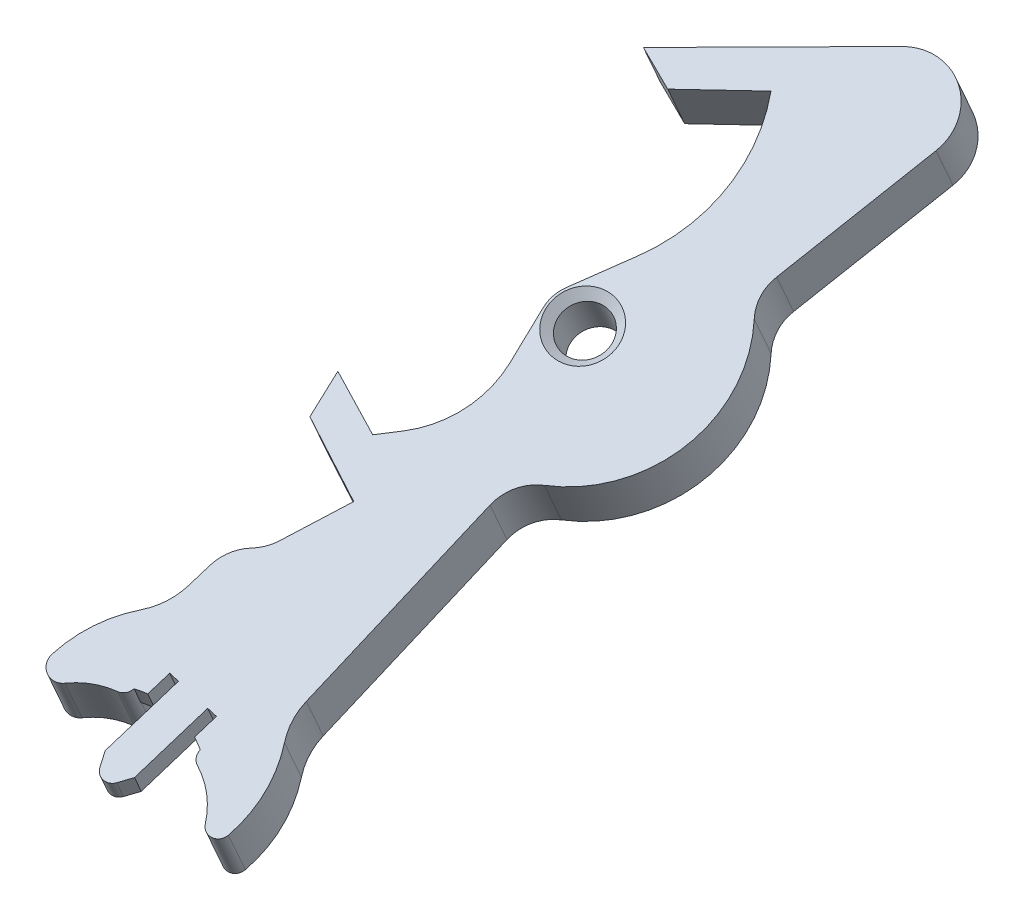
SolidWorks part; units mm, degrees
ref_plane "Plan de face" through (0, 0, 0) normal (0, 0, 1) x (1, 0, 0)
ref_plane "Plan de dessus" through (0, 0, 0) normal (0, 1, 0) x (1, 0, 0)
ref_plane "Plan de droite" through (0, 0, 0) normal (1, 0, 0) x (0, 0, -1)
ref_plane "Plan1" through (6.4076, 24.4468, 14.3554) normal (0.2205, 0.8411, 0.4939) x (-0.9673, 0.2535, 0)
sketch "Esquisse1" plane through (6.4076, 24.4468, 14.3554) normal (0.2205, 0.8411, 0.4939) x (-0.9673, 0.2535, 0)
  line L0 (8.3108, -19.2013) -> (8.287, -20.2463)
  line L1 (8.287, -20.2463) -> (5.8877, -20.1917)
  line L2 (5.8877, -20.1917) -> (5.9114, -19.1468)
  line L3 (5.4159, -18.9439) -> (5.4244, -18.5688)
  line L4 (3.8694, -21.6822) -> (4.3684, -33.2537)
  line L5 (2.9658, -43.5208) -> (2.0143, -51.4977)
  line L6 (5.7057, -53.4454) -> (12.5394, -47.4699)
  line L7 (12.5394, -47.4699) -> (10.7754, -46.9416)
  line L8 (10.7754, -46.9416) -> (7.9879, -49.2605)
  line L9 (7.0808, -41.9184) -> (8.3544, -38.9103)
  line L10 (8.3544, -38.9103) -> (6.9616, -33.8048)
  line L11 (6.9616, -33.8048) -> (9.3087, -31.1351)
  line L12 (9.3087, -31.1351) -> (11.9385, -31.9936)
  line L13 (11.9385, -31.9936) -> (11.4603, -30.1656)
  line L14 (11.4603, -30.1656) -> (8.02, -28.9566)
  line L15 (8.02, -28.9566) -> (8.9263, -26.2414)
  line L16 (10.1164, -23.9748) -> (10.1637, -21.8969)
  line L17 (8.8235, -18.6461) -> (8.815, -19.0212)
  arc A0 (5.9114, -19.1468) -> (5.4159, -18.9439) centre (7.6542, -14.1836) cw
  arc A1 (5.4244, -18.5688) -> (3.2945, -17.127) centre (6.1546, -15.196) cw
  arc A2 (3.2945, -17.127) -> (2.3817, -17.3668) centre (2.8801, -17.4067) ccw
  arc A3 (2.3817, -17.3668) -> (3.8694, -21.6822) centre (8.0635, -17.8222) ccw
  arc A4 (4.3684, -33.2537) -> (2.9658, -43.5208) centre (6.665, -38.7968) ccw
  arc A5 (2.0143, -51.4977) -> (5.7057, -53.4454) centre (4.2341, -51.7625) ccw
  arc A6 (7.9879, -49.2605) -> (7.0808, -41.9184) centre (13.8952, -44.8036) cw
  arc A7 (8.9263, -26.2414) -> (9.4702, -25.402) centre (10.8234, -26.8746) cw
  arc A8 (9.4702, -25.402) -> (10.1164, -23.9748) centre (8.1169, -23.9293) ccw
  arc A9 (10.1637, -21.8969) -> (11.9147, -18.0509) centre (6.2212, -17.7803) ccw
  arc A10 (11.9147, -18.0509) -> (10.7871, -17.58) centre (11.2655, -18.0201) ccw
  arc A11 (10.7871, -17.58) -> (8.8235, -18.6461) centre (8.2474, -15.2436) cw
  arc A12 (8.815, -19.0212) -> (8.3108, -19.2013) centre (6.7954, -14.1641) cw
extrude "Boss.-Extru.1" add sketch "Esquisse1" against normal blind 1.2
sketch "Esquisse2" plane through (6.143, 23.4375, 13.7628) normal (-0.2205, -0.8411, -0.4939) x (0.9754, -0.1901, -0.1116)
  line L0 (-7.7323, -33.2616) -> (-7.4927, -31.3873)
  line L1 (-7.4927, -31.3873) -> (-4.2361, -29.7466)
  line L2 (-4.2361, -29.7466) -> (-5.4835, -27.1702)
  line L3 (-6.9548, -25.0751) -> (-7.2684, -23.0206)
  line L4 (-6.3567, -19.6246) -> (-6.1135, -21.2181)
  line L5 (-6.1135, -21.2181) -> (-2.7524, -20.7051)
  line L6 (-2.7524, -20.7051) -> (-2.9956, -19.1115)
  line L7 (-1.0537, -21.9995) -> (-0.0631, -33.5394)
  line L8 (2.6461, -43.5414) -> (4.6138, -51.3301)
  line L9 (1.203, -53.7356) -> (-6.3413, -48.6869)
  line L10 (-6.3413, -48.6869) -> (-4.6597, -47.9365)
  line L11 (-4.6597, -47.9365) -> (-1.5976, -49.8784)
  line L12 (-1.6406, -42.4806) -> (-3.2899, -39.6609)
  line L13 (-3.2899, -39.6609) -> (-2.564, -34.4188)
  line L14 (-2.564, -34.4188) -> (-5.2344, -32.0726)
  line L15 (-5.2344, -32.0726) -> (-7.7323, -33.2616)
  arc A0 (-5.4835, -27.1702) -> (-6.1306, -26.4076) centre (-7.2836, -28.0418) ccw
  arc A1 (-6.1306, -26.4076) -> (-6.9548, -25.0751) centre (-4.9776, -24.7734) cw
  arc A2 (-7.2684, -23.0206) -> (-9.4987, -19.4312) centre (-3.887, -18.4318) cw
  arc A3 (-9.4987, -19.4312) -> (-8.4409, -18.8194) centre (-8.8588, -19.3172) cw
  arc A4 (-8.4409, -18.8194) -> (-6.3567, -19.6246) centre (-6.2221, -16.1763) ccw
  arc A5 (-2.9956, -19.1115) -> (-1.0684, -17.4082) centre (-4.1528, -15.8604) ccw
  arc A6 (-1.0684, -17.4082) -> (-0.1324, -17.5288) centre (-0.6215, -17.6324) cw
  arc A7 (-0.1324, -17.5288) -> (-1.0537, -21.9995) centre (-5.7087, -18.7099) cw
  arc A8 (-0.0631, -33.5394) -> (2.6461, -43.5414) centre (-1.629, -39.3314) cw
  arc A9 (4.6138, -51.3301) -> (1.203, -53.7356) centre (2.4464, -51.8777) cw
  arc A10 (-1.5976, -49.8784) -> (-1.6406, -42.4806) centre (-8.0282, -46.2167) ccw
extrude "Boss.-Extru.2" add sketch "Esquisse2" along normal blind 1.8
sketch "Esquisse3" plane through (6.4076, 24.4468, 14.3554) normal (0.2205, 0.8411, 0.4939) x (-0.9673, 0.2535, 0)
  line L0 (7.8372, -20.2361) -> (7.9165, -16.7452)
  line L1 (7.9165, -16.7452) -> (7.6121, -16.1891)
  line L2 (6.7463, -16.1694) -> (6.4169, -16.7111)
  line L3 (6.4169, -16.7111) -> (6.3375, -20.202)
  line L4 (6.3375, -20.202) -> (7.8372, -20.2361)
  arc A0 (7.6121, -16.1891) -> (6.7463, -16.1694) centre (7.1735, -16.4292) ccw
extrude "Boss.-Extru.3" add sketch "Esquisse3" against normal blind 1.2
sketch "Esquisse4" plane through (2.9513, 9.4625, -17.4316) normal (-0.1472, -0.4719, 0.8693) x (0.9891, -0.0702, 0.1293)
  line L0 (0.5126, 28.467) -> (-2.8018, 29.2248)
  line L1 (-2.8018, 29.2248) -> (-3.203, 27.4701)
  line L2 (-3.203, 27.4701) -> (0.1115, 26.7123)
  line L3 (0.1115, 26.7123) -> (0.5126, 28.467)
extrude "Enlèv. mat.-Extru.1" cut sketch "Esquisse4" against normal blind 0.5
hole_wizard "Dégagement #11" positions "Esquisse6" profile "Esquisse5" hole size "#1" standard "Ansi Inch"
sketch "Esquisse6" plane through (6.4076, 24.4468, 14.3554) normal (0.2205, 0.8411, 0.4939) x (0.9754, -0.1901, -0.1116)
  point P0 (-1.629, 39.3314)
sketch "Esquisse5" plane through (4.8187, 44.6725, -19.379) normal (0.6062, -0.5148, 0.6062) x (-0.7642, -0.1658, 0.6234)
  line L0 (0, 0) -> (0, 20.853)
  line L1 (0, 20.853) -> (1.1, 20.853)
  line L2 (1.1, 20.853) -> (1.1, 0)
  line L5 (1.1, 0) -> (0, 0)
  line L11 (0, -6.35) -> (0, 107.95) construction
  dimension "Diamètre du perçage jusqu'au prochain" = 2.2
  dimension "Profondeur du perçage jusqu'au prochain" = 20.853
chamfer "Chanfrein1" distance 0.4 angle 45 2 edges at (4.1573, 42.7062, -21.8093) (4.8187, 44.1155, -18.4304)
fillet "Congé1" radius 0.5 2 edges at (-0.1234, 34.3308, -2.5985) (3.155, 33.4321, -2.5313) tangent propagation no
fillet "Congé2" radius 1.6 1 edges at (2.868, 43.8934, -20.2185) tangent propagation no
fillet "Congé3" radius 2 2 edges at (8.6579, 44.7299, -24.2274) (6.0154, 40.1803, -15.3) tangent propagation no
fillet "Congé4" radius 3 2 edges at (5.0491, 34.5253, -5.2384) (-1.0126, 36.2237, -5.4251) tangent propagation no
fillet "Congé5" radius 4.6 1 edges at (3.576, 41.1011, -15.7792) tangent propagation no
